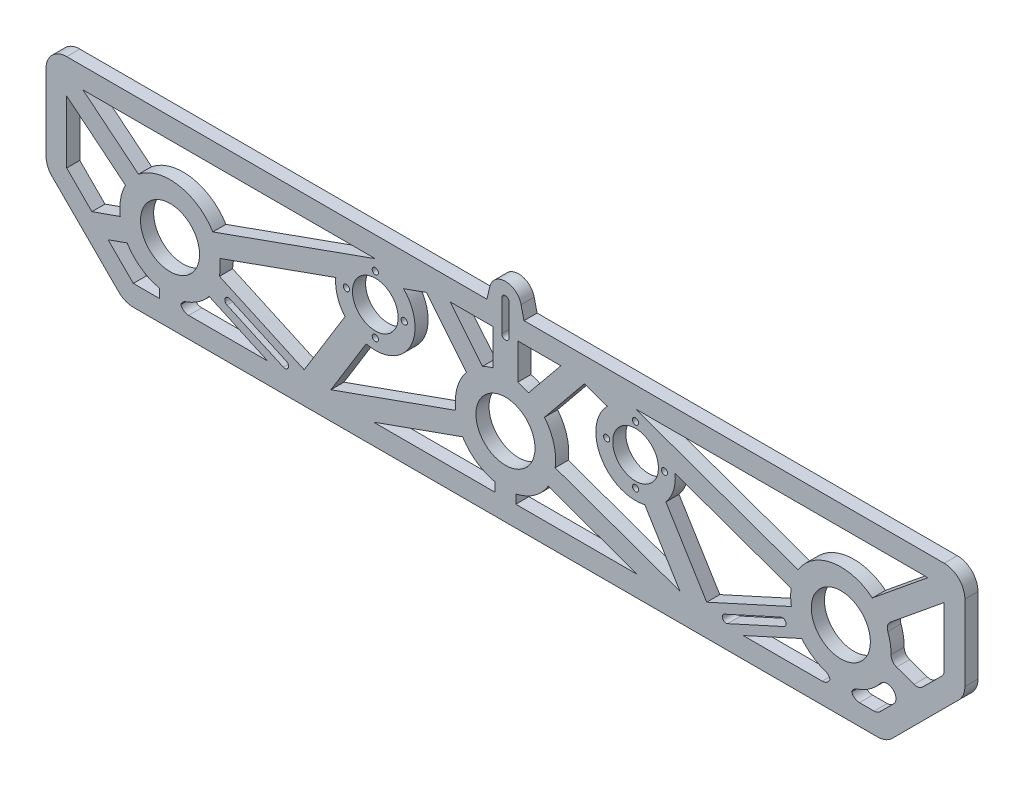
SolidWorks part; units mm, degrees
material "6061 Alloy"
ref_plane "Front Plane" through (0, 0, 0) normal (0, 0, 1) x (1, 0, 0)
ref_plane "Top Plane" through (0, 0, 0) normal (0, 1, 0) x (1, 0, 0)
ref_plane "Right Plane" through (0, 0, 0) normal (1, 0, 0) x (0, 0, -1)
sketch "Sketch1" plane through (0, 0, 0) normal (0, 0, 1) x (1, 0, 0)
  line L0 (2.9289, 35.1711) -> (35.1711, 2.9289)
  line L1 (42.2421, 0) -> (402.2579, 0)
  line L2 (0, 42.2421) -> (0, 78.9)
  line L3 (10, 88.9) -> (434.5, 88.9)
  line L4 (444.5, 42.2421) -> (444.5, 78.9)
  line L5 (409.3289, 2.9289) -> (441.5711, 35.1711)
  line L6 (222.25, 88.9) -> (222.25, 78.9) construction
  line L7 (42.2421, 10) -> (55, 10)
  line L8 (402.2579, 10) -> (414.4609, 22.2031)
  line L9 (434.5, 42.2421) -> (434.5, 72.4466)
  line L10 (17.9086, 78.9) -> (159.3033, 78.9)
  line L11 (10, 42.2421) -> (10, 72.4466)
  line L12 (10, 42.2421) -> (22.2031, 30.0391)
  line L13 (24.4543, 30.8351) -> (22.2031, 30.0391)
  line L14 (30.0391, 22.2031) -> (42.2421, 10)
  line L15 (10, 42.2421) -> (42.2421, 10) construction
  line L16 (44.7466, 57.0002) -> (17.9086, 78.9)
  line L17 (30.0391, 22.2031) -> (39.259, 25.463)
  line L18 (55, 14.3327) -> (55, 10)
  line L19 (38.4244, 49.2523) -> (10, 72.4466)
  line L20 (24.4543, 30.8351) -> (35.9254, 34.891)
  line L21 (65, 14.3327) -> (65, 10)
  line L22 (399.7534, 57.0002) -> (426.5914, 78.9)
  line L23 (65, 10) -> (128.7681, 10)
  line L24 (10, 78.9) -> (434.5, 78.9) construction
  line L25 (42.2421, 10) -> (402.2579, 10) construction
  line L26 (10, 42.2421) -> (10, 78.9) construction
  line L27 (185.1403, 75.7423) -> (203.3633, 53.37)
  line L28 (175.8429, 74.1917) -> (184.0222, 77.1149)
  line L29 (80.6981, 50.8071) -> (159.3033, 78.9)
  line L30 (84.0636, 41.3904) -> (140.1692, 61.4422)
  line L31 (158.4819, 10) -> (201.5519, 25.3929)
  line L32 (141.9423, 14.7083) -> (198.1864, 34.8096)
  line L33 (195.4658, 78.9) -> (211.1167, 59.6855)
  line L34 (185.1403, 75.7423) -> (184.0222, 77.1149)
  line L35 (406.0756, 49.2523) -> (434.5, 72.4466)
  line L36 (195.4658, 78.9) -> (249.0342, 78.9)
  line L37 (158.4819, 10) -> (217.25, 10)
  line L38 (217.25, 14.3327) -> (217.25, 10)
  line L39 (141.9423, 14.7083) -> (128.7681, 10)
  line L40 (420.0457, 30.8351) -> (422.2969, 30.0391)
  line L41 (420.0457, 30.8351) -> (408.5746, 34.891)
  line L42 (379.5, 14.3327) -> (379.5, 10)
  line L43 (389.5, 14.3327) -> (389.5, 10)
  line L44 (414.4609, 22.2031) -> (405.241, 25.463)
  line L45 (414.4609, 22.2031) -> (402.2579, 10)
  line L46 (402.2579, 10) -> (389.5, 10)
  line L47 (379.5, 10) -> (315.7319, 10)
  line L48 (286.0181, 10) -> (227.25, 10)
  line L49 (302.5577, 14.7083) -> (315.7319, 10)
  line L50 (302.5577, 14.7083) -> (246.3136, 34.8096)
  line L51 (286.0181, 10) -> (242.9481, 25.3929)
  line L52 (363.8019, 50.8071) -> (285.1967, 78.9)
  line L53 (360.4364, 41.3904) -> (304.3308, 61.4422)
  line L54 (268.6571, 74.1917) -> (260.4778, 77.1149)
  line L55 (259.3597, 75.7423) -> (260.4778, 77.1149)
  line L56 (249.0342, 78.9) -> (233.3833, 59.6855)
  line L57 (259.3597, 75.7423) -> (241.1367, 53.37)
  line L58 (285.1967, 78.9) -> (426.5914, 78.9)
  line L59 (422.2969, 30.0391) -> (434.5, 42.2421)
  line L60 (402.2579, 10) -> (434.5, 42.2421) construction
  line L61 (434.5, 42.2421) -> (434.5, 78.9) construction
  line L62 (227.25, 10) -> (227.25, 14.3327)
  line L63 (271.5104, 73.1719) -> (268.6571, 74.1917)
  line L64 (172.9896, 73.1719) -> (175.8429, 74.1917)
  arc A0 (434.5, 88.9) -> (444.5, 78.9) centre (434.5, 78.9) cw
  arc A1 (441.5711, 35.1711) -> (444.5, 42.2421) centre (434.5, 42.2421) ccw
  arc A2 (409.3289, 2.9289) -> (402.2579, 0) centre (402.2579, 10) cw
  arc A3 (35.1711, 2.9289) -> (42.2421, 0) centre (42.2421, 10) ccw
  arc A4 (2.9289, 35.1711) -> (0, 42.2421) centre (10, 42.2421) cw
  arc A5 (0, 78.9) -> (10, 88.9) centre (10, 78.9) cw
  circle A6 centre (60, 38.1) radius 14.2875
  circle A8 centre (384.5, 38.1) radius 14.2875
  arc A9 (402.2579, 10) -> (402.2579, 10) centre (402.2579, 10) cw
  arc A10 (434.5, 42.2421) -> (434.5, 42.2421) centre (434.5, 42.2421) ccw
  arc A11 (434.5, 78.9) -> (434.5, 78.9) centre (434.5, 78.9) cw
  arc A12 (10, 78.9) -> (10, 78.9) centre (10, 78.9) cw
  arc A13 (10, 42.2421) -> (10, 42.2421) centre (10, 42.2421) cw
  arc A14 (42.2421, 10) -> (42.2421, 10) centre (42.2421, 10) ccw
  arc A15 (38.4244, 49.2523) -> (35.9254, 34.891) centre (60, 38.1) ccw
  arc A16 (201.5519, 25.3929) -> (217.25, 14.3327) centre (222.25, 38.1) ccw
  arc A17 (363.8019, 50.8071) -> (399.7534, 57.0002) centre (384.5, 38.1) cw
  circle A18 centre (60, 38.1) radius 24.2875 construction
  arc A19 (39.259, 25.463) -> (55, 14.3327) centre (60, 38.1) ccw
  arc A20 (65, 14.3327) -> (84.0636, 41.3904) centre (60, 38.1) ccw
  arc A21 (80.6981, 50.8071) -> (44.7466, 57.0002) centre (60, 38.1) ccw
  circle A22 centre (222.25, 38.1) radius 14.2875
  arc A23 (203.3633, 53.37) -> (198.1864, 34.8096) centre (222.25, 38.1) ccw
  arc A24 (227.25, 14.3327) -> (242.9481, 25.3929) centre (222.25, 38.1) ccw
  arc A25 (246.3136, 34.8096) -> (241.1367, 53.37) centre (222.25, 38.1) ccw
  arc A26 (233.3833, 59.6855) -> (211.1167, 59.6855) centre (222.25, 38.1) ccw
  circle A27 centre (384.5, 38.1) radius 24.2875 construction
  arc A28 (406.0756, 49.2523) -> (408.5746, 34.891) centre (384.5, 38.1) cw
  arc A29 (379.5, 14.3327) -> (360.4364, 41.3904) centre (384.5, 38.1) cw
  arc A30 (405.241, 25.463) -> (389.5, 14.3327) centre (384.5, 38.1) cw
  circle A31 centre (159.3033, 59.6855) radius 11.049
  arc A34 (140.1692, 61.4422) -> (172.9896, 73.1719) centre (159.3033, 59.6855) ccw
  circle A35 centre (159.3033, 73.6809) radius 1.5
  circle A36 centre (145.3079, 59.6855) radius 1.5
  circle A37 centre (159.3033, 45.6901) radius 1.5
  circle A38 centre (173.2987, 59.6855) radius 1.5
  arc A39 (304.3308, 61.4422) -> (271.5104, 73.1719) centre (285.1967, 59.6855) cw
  circle A40 centre (285.1967, 45.6901) radius 1.5
  circle A41 centre (285.1967, 73.6809) radius 1.5
  circle A42 centre (271.2013, 59.6855) radius 1.5
  circle A43 centre (299.1921, 59.6855) radius 1.5
  circle A44 centre (285.1967, 59.6855) radius 11.049
  point P0 (0, 0)
  point P3 (444.5, 0)
  point P13 (444.5, 38.1)
  point P16 (406.4, 0)
  point P19 (38.1, 0)
  point P22 (0, 38.1)
  point P25 (0, 88.9)
  point P132 (159.3033, 59.6855)
  dimension "D3" = 10
  dimension "D4" = 28.575
  dimension "D5" = 28.575
  dimension "D12" = 22.098
  dimension "D15" = 3
  dimension "D1" = 88.9
  dimension "D2" = 444.5
  dimension "D8" = 60
  dimension "D9" = 10
  dimension "D10" = 10
  dimension "D11" = 10
  dimension "D16" = 4
extrude "Boss-Extrude1" add sketch "Sketch1" along normal blind 6.35 contours A5 L2 A4 L0 A3 L1 A2 L5 A1 L4 A0 L3 A30 L44 L8 L46 L43 A29 L42 L47 L49 L50 A25 L57 L55 L54 L53 A28 L35 L9 L59 L40 L41 A22 A17 L52 L58 L22 A6 A8 L19 A15 L20 region at (4.9492, 40.15, 0)
fillet "Fillet3" radius 4 13 edges at (434.5, 42.2421, 3.175) (422.2969, 30.0391, 3.175) (408.5746, 34.891, 3.175) (406.0756, 49.2523, 3.175) (414.4609, 22.2031, 3.175) (405.241, 25.463, 3.175) (402.2579, 10, 3.175) (389.5, 10, 3.175) (389.5, 14.3327, 3.175) (65, 10, 3.175) (65, 14.3327, 3.175) (379.5, 14.3327, 3.175) (379.5, 10, 3.175)
sketch "Sketch2" plane through (0, 0, 6.35) normal (0, 0, 1) x (1, 0, 0)
  line L0 (216.25, 62.3875) -> (216.25, 61.6347)
  line L2 (228.25, 62.3875) -> (228.25, 78.9)
  line L3 (216.25, 62.3875) -> (216.25, 78.9)
  line L4 (228.25, 62.3875) -> (228.25, 61.6347)
  line L6 (195.4658, 78.9) -> (249.0342, 78.9) construction
  line L9 (216.25, 78.9) -> (228.25, 78.9)
  arc A0 (228.25, 61.6347) -> (216.25, 61.6347) centre (222.25, 38.1) ccw
  arc A1 (233.3833, 59.6855) -> (211.1167, 59.6855) centre (222.25, 38.1) ccw construction
extrude "Boss-Extrude2" add sketch "Sketch2" against normal up to surface (6.35 mm away) up to face at (300.6921, 59.6855, 0)
sketch "Sketch3" plane through (0, 0, 6.35) normal (0, 0, 1) x (1, 0, 0)
  line L0 (229.8221, 94.878) -> (231.8491, 86.2454)
  line L3 (231.8491, 86.2454) -> (222.25, 85.322)
  line L4 (214.6779, 94.878) -> (212.4341, 85.322)
  line L5 (212.4341, 85.322) -> (222.25, 85.322)
  circle A2 centre (222.25, 93.1) radius 1.778
  circle A3 centre (222.25, 93.1) radius 7.778
  dimension "D2" = 3.556
  dimension "D1" = 6
extrude "Boss-Extrude3" add sketch "Sketch3" against normal up to surface (6.35 mm away) contours A3 L3 A2 | A3 L4 L5 | A3 L3 L0 region at (229.4014, 88.0302, 6.35) region at (229.7578, 93.9696, 6.35) region at (215.2292, 87.5368, 6.35) up to face at (209.7568, 69.8164, 0)
sketch "Sketch5" plane through (0, 0, 0) normal (0, 0, -1) x (-1, 0, 0)
  line L0 (-320.8437, 13.1416) -> (-322.7744, 10)
  line L1 (-123.6563, 13.1416) -> (-121.7256, 10)
  line L2 (-154.8576, 40.9923) -> (-137.7929, 13.2254)
  line L3 (-299.8661, 47.2754) -> (-320.8437, 13.1416)
  line L4 (-144.6339, 47.2754) -> (-123.6563, 13.1416)
  line L5 (-289.6424, 40.9923) -> (-306.7071, 13.2254)
  line L6 (-69, 10) -> (-128.7681, 10) construction
  line L7 (-128.7681, 10) -> (-198.1864, 34.8096) construction
  line L8 (-375.5, 10) -> (-315.7319, 10) construction
  line L9 (-246.3136, 34.8096) -> (-315.7319, 10) construction
  line L10 (-69, 10) -> (-128.7681, 10)
  line L11 (-128.7681, 10) -> (-198.1864, 34.8096)
  line L12 (-375.5, 10) -> (-315.7319, 10)
  line L13 (-246.3136, 34.8096) -> (-315.7319, 10)
  line L16 (-311.8189, 16.3669) -> (-297.1583, 40.222) construction
  line L17 (-313.3337, 17.2979) -> (-298.6731, 41.153)
  line L18 (-310.3041, 15.436) -> (-295.6435, 39.2911)
  line L19 (-132.6811, 16.3669) -> (-147.3417, 40.222) construction
  line L20 (-134.1959, 15.436) -> (-148.8565, 39.2911)
  line L21 (-131.1663, 17.2979) -> (-145.8269, 41.153)
  arc A0 (-172.9896, 73.1719) -> (-140.1692, 61.4422) centre (-159.3033, 59.6855) ccw construction
  arc A1 (-304.3308, 61.4422) -> (-271.5104, 73.1719) centre (-285.1967, 59.6855) ccw construction
  arc A2 (-172.9896, 73.1719) -> (-140.1692, 61.4422) centre (-159.3033, 59.6855) ccw
  arc A3 (-304.3308, 61.4422) -> (-271.5104, 73.1719) centre (-285.1967, 59.6855) ccw
  arc A4 (-313.3337, 17.2979) -> (-310.3041, 15.436) centre (-311.8189, 16.3669) ccw
  arc A5 (-295.6435, 39.2911) -> (-298.6731, 41.153) centre (-297.1583, 40.222) ccw
  arc A6 (-134.1959, 15.436) -> (-131.1663, 17.2979) centre (-132.6811, 16.3669) ccw
  arc A7 (-145.8269, 41.153) -> (-148.8565, 39.2911) centre (-147.3417, 40.222) ccw
  point P26 (-304.4886, 28.2945)
  point P32 (-140.0114, 28.2945)
extrude "Boss-Extrude4" add sketch "Sketch5" against normal blind 6.35 contours A3 L3 L0 L12 L13 L5 A5 L18 A4 L17 | A2 L2 L11 L10 L1 L4 A7 L21 A6 L20 | L21 A7 L20 A6 | L18 A5 L17 A4 region at (309.93, 29.9474, 0) region at (123.1159, 11.3097, 0) region at (304.4886, 28.2945, 0) region at (140.0114, 28.2945, 0)
sketch "Sketch6" plane through (0, 0, 6.35) normal (0, 0, 1) x (1, 0, 0)
  line L0 (222.25, 38.1) -> (222.25, 4.6334)
  line L1 (78.9336, 22.8882) -> (107.2443, 10)
  line L2 (83.9056, 33.8097) -> (124.2116, 15.4608)
  line L3 (144.6339, 47.2754) -> (121.7256, 10) construction
  line L4 (69, 10) -> (121.7256, 10) construction
  line L5 (124.8914, 15.1513) -> (121.7256, 10)
  line L6 (69, 10) -> (121.7256, 10)
  line L7 (320.2884, 15.4608) -> (319.6086, 15.1513)
  line L8 (124.2116, 15.4608) -> (124.8914, 15.1513)
  line L9 (319.6086, 15.1513) -> (322.7744, 10)
  line L10 (356.2367, 25.2334) -> (328.9329, 12.8036) construction
  line L11 (88.2633, 25.2334) -> (115.5671, 12.8036) construction
  line L12 (88.9999, 26.8516) -> (116.3038, 14.4218)
  line L13 (87.5266, 23.6152) -> (114.8304, 11.1854)
  line L14 (355.5001, 26.8516) -> (328.1962, 14.4218)
  line L15 (356.9734, 23.6152) -> (329.6696, 11.1854)
  line L16 (360.5944, 33.8097) -> (320.2884, 15.4608)
  line L17 (365.5664, 22.8882) -> (337.2557, 10)
  line L18 (322.7744, 10) -> (337.2557, 10)
  arc A0 (67.7274, 15.0746) -> (84.0636, 41.3904) centre (60, 38.1) ccw construction
  arc A1 (67.7274, 15.0746) -> (84.0636, 41.3904) centre (60, 38.1) ccw
  arc A2 (88.9999, 26.8516) -> (87.5266, 23.6152) centre (88.2633, 25.2334) ccw
  arc A3 (114.8304, 11.1854) -> (116.3038, 14.4218) centre (115.5671, 12.8036) ccw
  arc A4 (365.5664, 22.8882) -> (360.5944, 33.8097) centre (384.5, 38.1) cw
  arc A5 (355.5001, 26.8516) -> (356.9734, 23.6152) centre (356.2367, 25.2334) cw
  arc A6 (329.6696, 11.1854) -> (328.1962, 14.4218) centre (328.9329, 12.8036) cw
  point P21 (101.9152, 19.0185)
  point P31 (342.5848, 19.0185)
extrude "Boss-Extrude5" add sketch "Sketch6" against normal blind 6.35 contours A1 L1 L6 L5 L8 L2 A3 L13 A2 L12 | L17 A4 L16 L7 L9 L18 L15 A6 L14 A5 region at (82.5758, 27.8226, 6.35) region at (340.6559, 24.1642, 6.35)
sketch "Sketch7" plane through (0, 0, 6.35) normal (0, 0, 1) x (1, 0, 0)
  line L0 (222.25, 93.1) -> (222.25, 78.1) construction
  line L1 (224.028, 93.1) -> (224.028, 78.1)
  line L2 (220.472, 93.1) -> (220.472, 78.1)
  arc A0 (224.028, 93.1) -> (220.472, 93.1) centre (222.25, 93.1) ccw
  arc A1 (220.472, 78.1) -> (224.028, 78.1) centre (222.25, 78.1) ccw
  point P3 (222.25, 85.6)
extrude "Cut-Extrude1" cut sketch "Sketch7" against normal blind 10
